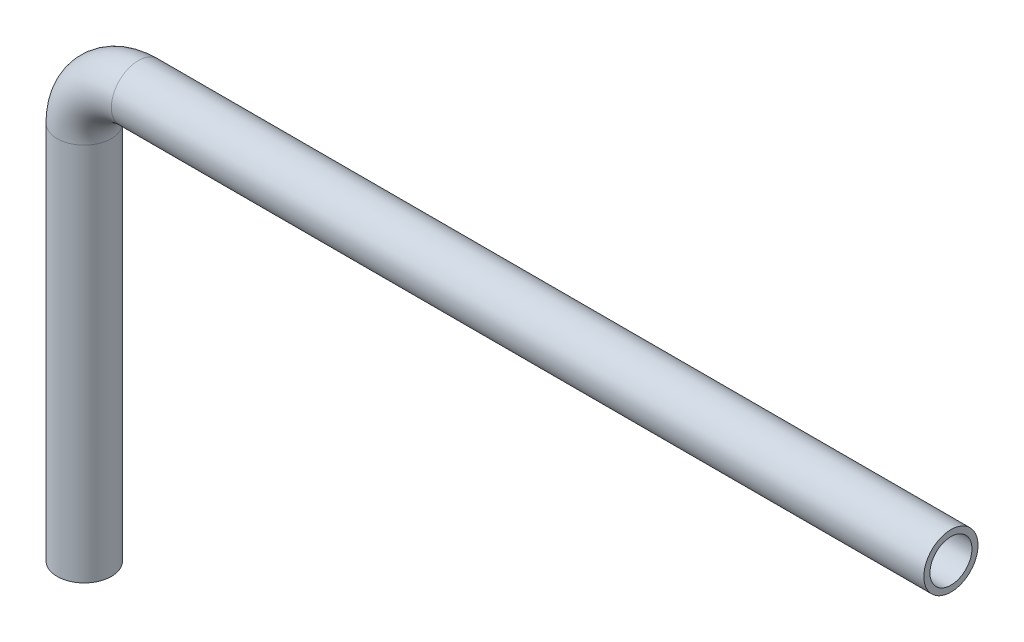
SolidWorks part; units mm, degrees
ref_plane "Front Plane" through (0, 0, 0) normal (0, 0, 1) x (1, 0, 0)
ref_plane "Top Plane" through (0, 0, 0) normal (0, 1, 0) x (1, 0, 0)
ref_plane "Right Plane" through (0, 0, 0) normal (1, 0, 0) x (0, 0, -1)
sketch "Sketch1" plane through (0, 0, 0) normal (0, 1, 0) x (1, 0, 0)
  circle A0 centre (0, 0) radius 1.5875
  circle A1 centre (0, 0) radius 1.2319
  dimension "D1" = 3.175
  dimension "D2" = 2.4638
sketch "Sketch2" plane through (0, 0, 0) normal (0, 0, 1) x (1, 0, 0)
  line L0 (0, 0) -> (0, 22.225)
  line L1 (1.5875, 0) -> (-1.5875, 0) construction
  line L2 (3.175, 25.4) -> (50.8, 25.4)
  arc A0 (0, 22.225) -> (3.175, 25.4) centre (3.175, 22.225) cw
  point P7 (0, 25.4)
  dimension "D3" = 3.175
  dimension "D1" = 25.4
  dimension "D2" = 50.8
sweep "Sweep1" add profiles "Sketch1" path "Sketch2"
